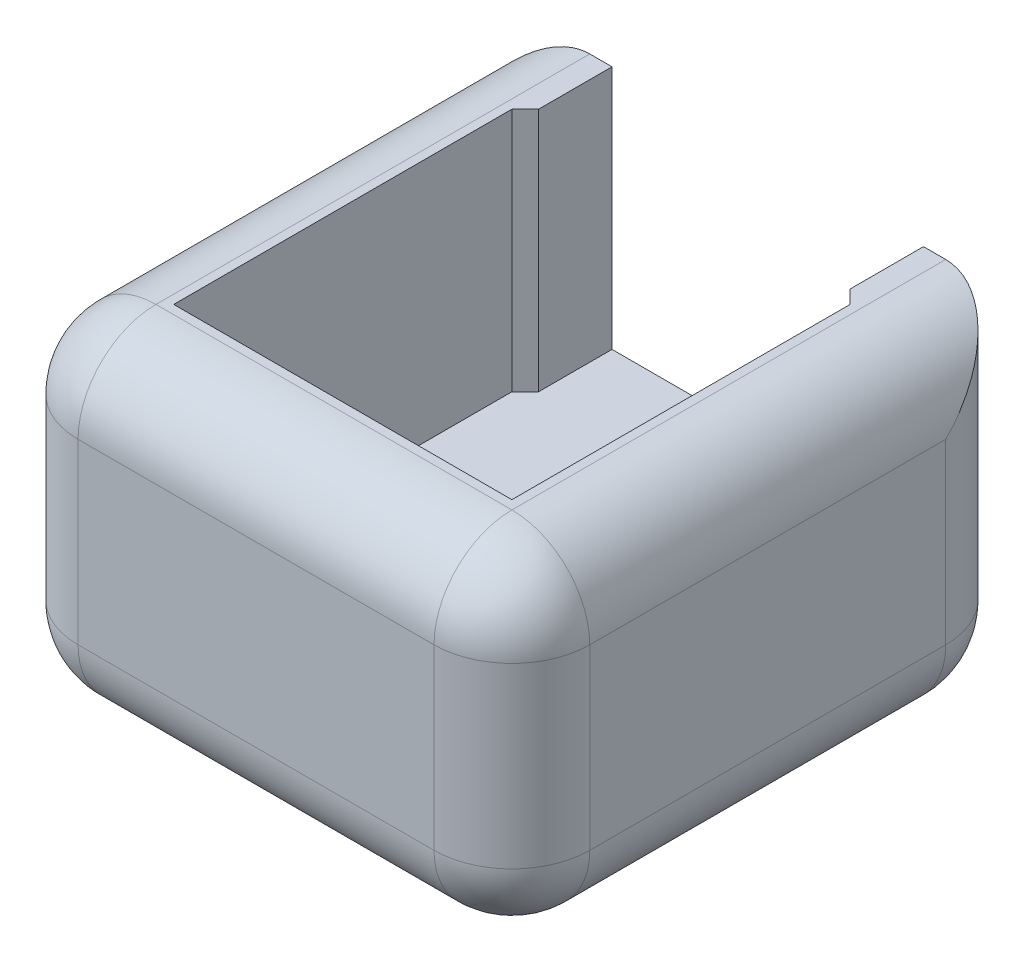
SolidWorks part; units mm, degrees
ref_plane "前视基准面" through (0, 0, 0) normal (0, 0, 1) x (1, 0, 0)
ref_plane "上视基准面" through (0, 0, 0) normal (0, 1, 0) x (1, 0, 0)
ref_plane "右视基准面" through (0, 0, 0) normal (1, 0, 0) x (0, 0, -1)
sketch "草图1" plane through (0, 0, 0) normal (0, 1, 0) x (1, 0, 0)
  line L1 (-23, -23) -> (23, -23)
  line L2 (-23, -23) -> (-23, 23)
  line L3 (-23, 23) -> (23, 23)
  line L4 (23, -23) -> (23, 23)
  line L5 (0, 23) -> (0, -23) construction
  line L6 (-23, 0) -> (23, 0) construction
  point P0 (0, 0)
  dimension "D1" = 46
extrude "凸台-拉伸1" add sketch "草图1" along normal blind 30
sketch "草图2" plane through (0, 30, 0) normal (0, 1, 0) x (1, 0, 0)
  line L1 (-15.2, -15.2) -> (15.2, -15.2)
  line L2 (-15.2, -15.2) -> (-15.2, 15.2)
  line L3 (-15.2, 15.2) -> (15.2, 15.2)
  line L4 (15.2, -15.2) -> (15.2, 15.2)
  line L5 (0, 15.2) -> (0, -15.2) construction
  line L6 (-15.2, 0) -> (15.2, 0) construction
  point P0 (0, 0)
  dimension "D1" = 30.4
extrude "切除-拉伸1" cut sketch "草图2" against normal offset from surface (22 mm away) 8 up to face at (0, 0, 0)
sketch "草图3" plane through (0, 30, 0) normal (0, 1, 0) x (1, 0, 0)
  line L0 (15.2, 15.2) -> (-15.2, 15.2) construction
  line L1 (-14, 23) -> (14, 23)
  line L2 (-14, 23) -> (-14, 15.2)
  line L3 (-14, 15.2) -> (14, 15.2)
  line L4 (14, 23) -> (14, 15.2)
  line L5 (0, 15.2) -> (0, 23) construction
  line L6 (-14, 19.1) -> (14, 19.1) construction
  line L7 (23, 23) -> (-23, 23) construction
  line L8 (15.2, -15.2) -> (15.2, 15.2) construction
  point P0 (0, 19.1)
  dimension "D1" = 1.2
extrude "切除-拉伸2" cut sketch "草图3" against normal up to surface (22 mm away) up to face at (0, 8, 0)
fillet "圆角1" radius 7 11 edges at (0, 0, -23) (-23, 0, 0) (0, 0, 23) (23, 0, 0) (0, 30, 23) (23, 30, 0) (-23, 30, 0) (-23, 15, -23) (-23, 15, 23) (23, 15, 23) (23, 15, -23)
hole_wizard "M6 六角头螺钉的柱形沉头孔1" positions "草图4" profile "草图5" counterbore size "M6" standard "ANSI Metric" end condition through all
sketch "草图4" plane through (0, 0, 0) normal (0, -1, 0) x (-1, 0, 0)
  point P0 (0, 0)
sketch "草图5" plane through (0, 0, 0) normal (1, 0, 0) x (0, 0, -1)
  line L0 (0, 0) -> (0, 30)
  line L1 (0, 30) -> (3.1, 30)
  line L3 (3.1, 30) -> (3.1, 5)
  line L4 (3.1, 5) -> (5.5, 5)
  line L5 (5.5, 5) -> (5.5, 0)
  line L7 (5.5, 0) -> (0, 0)
  line L11 (0, -6.35) -> (0, 107.95) construction
  dimension "通孔孔直径" = 6.2
  dimension "通孔孔深度" = 30
  dimension "柱形沉头孔直径" = 11
  dimension "柱形沉头孔深度" = 5
chamfer "倒角1" distance 1.2 angle 45 2 edges at (14, 19, -15.2) (-14, 19, -15.2)
